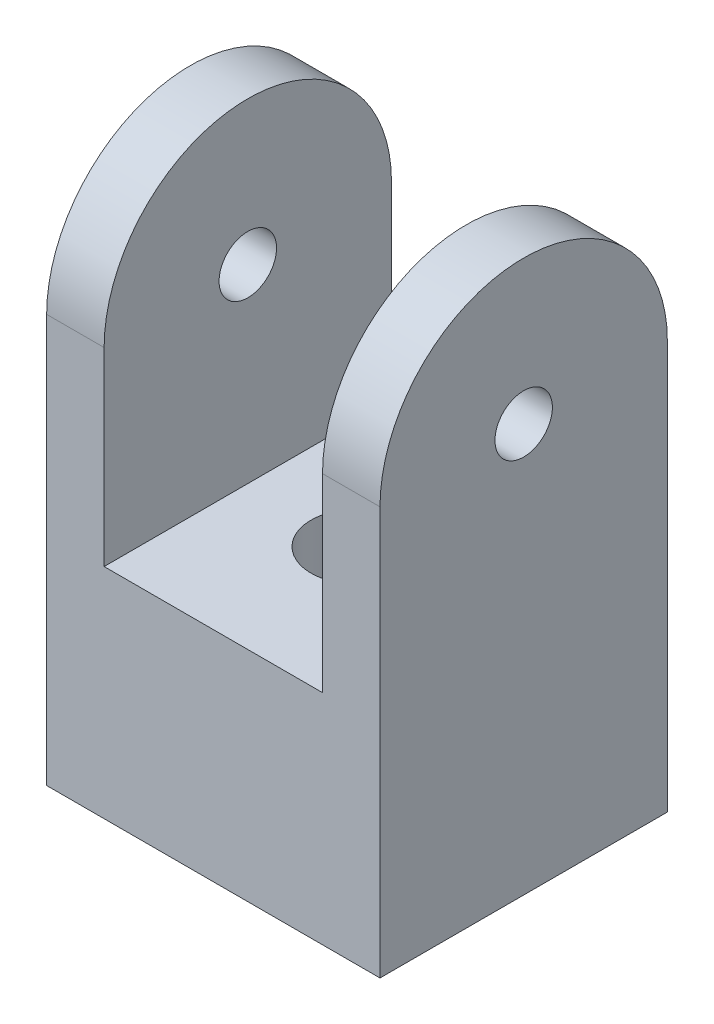
SolidWorks part; units mm, degrees
material "Polybutadiene (PB)"
ref_plane "Front Plane" through (0, 0, 0) normal (0, 0, 1) x (1, 0, 0)
ref_plane "Top Plane" through (0, 0, 0) normal (0, 1, 0) x (1, 0, 0)
ref_plane "Right Plane" through (0, 0, 0) normal (1, 0, 0) x (0, 0, -1)
sketch "Sketch1" plane through (0, 0, 0) normal (0, 0, 1) x (1, 0, 0)
  line L1 (0, 0) -> (29, 0)
  line L2 (0, 0) -> (0, 50)
  line L3 (0, 50) -> (29, 50)
  line L4 (29, 0) -> (29, 50)
  dimension "D1" = 29
  dimension "D2" = 50
extrude "Boss-Extrude1" add sketch "Sketch1" along normal blind 25
sketch "Sketch2" plane through (0, 0, 25) normal (0, 0, 1) x (1, 0, 0)
  line L0 (14.5, 50) -> (14.5, 11.8953) construction
  line L1 (29, 50) -> (0, 50) construction
  line L3 (5, 79) -> (24, 79)
  line L4 (5, 79) -> (5, 21)
  line L5 (5, 21) -> (24, 21)
  line L6 (24, 79) -> (24, 21)
  line L7 (5, 79) -> (24, 21) construction
  line L8 (5, 21) -> (24, 79) construction
  dimension "D1" = 19
  dimension "D2" = 58
extrude "Cut-Extrude1" cut sketch "Sketch2" against normal blind 25
fillet "Fillet2" 2 edges at (26.5, 50, 25) (26.5, 50, 0) type full round first side face at (14.5, 30.25, 25) second side face at (14.5, 30.25, 0) middle face at (26.5, 50, 12.5)
fillet "Fillet3" 2 edges at (2.5, 50, 25) (2.5, 50, 0) type full round first side face at (14.5, 27.125, 25) second side face at (14.5, 27.125, 0) middle face at (2.5, 50, 12.5)
sketch "Sketch3" plane through (0, 0, 0) normal (0, -1, 0) x (1, 0, 0)
  line L0 (29, 12.5) -> (11.8962, 12.5) construction
  line L1 (29, 25) -> (29, 0) construction
  line L2 (11.8962, 12.5) -> (14.5, 0) construction
  line L3 (0, 0) -> (29, 0) construction
  line L4 (14.5, 0) -> (14.5, 13.0424) construction
  circle A0 centre (14.5, 12.5) radius 4
  dimension "D1" = 8
extrude "Cut-Extrude2" cut sketch "Sketch3" against normal blind 25
sketch "Sketch4" plane through (29, 0, 0) normal (1, 0, 0) x (0, 0, -1)
  arc A0 (0, 37.5) -> (-25, 37.5) centre (-12.5, 37.5) ccw construction
  circle A1 centre (-12.5, 37.5) radius 2.5
  point P0 (-12.5, 37.5)
  dimension "D1" = 5
extrude "Cut-Extrude3" cut sketch "Sketch4" against normal blind 45
sketch "Sketch5" plane through (0, 0, 0) normal (0, 0, -1) x (-1, 0, 0)
  line L0 (-14.5, 21) -> (-14.5, 0) construction
  line L1 (-5, 21) -> (-24, 21) construction
  line L2 (-14.5, 0) -> (0, 10.5) construction
  line L3 (0, 37.5) -> (0, 0) construction
  line L4 (0, 10.5) -> (-29, 10.5) construction
  line L5 (0, 0) -> (-29, 0) construction
  line L6 (-24, 5) -> (-5, 5)
  line L7 (-24, 5) -> (-24, 16)
  line L8 (-24, 16) -> (-5, 16)
  line L9 (-5, 5) -> (-5, 16)
  line L10 (-24, 5) -> (-5, 16) construction
  line L11 (-24, 16) -> (-5, 5) construction
  line L12 (-29, 0) -> (-29, 37.5) construction
  point P8 (-14.5, 10.5)
  dimension "D1" = 5
  dimension "D2" = 5
  dimension "D3" = 5
extrude "Cut-Extrude4" cut sketch "Sketch5" against normal offset from surface (20 mm away) 5 up to face at (14.5, 24, 25)
chamfer "Chamfer1" distance 2 angle 45 4 edges at (29, 0, 12.5) (14.5, 0, 25) (0, 0, 12.5) (14.5, 0, 0)
